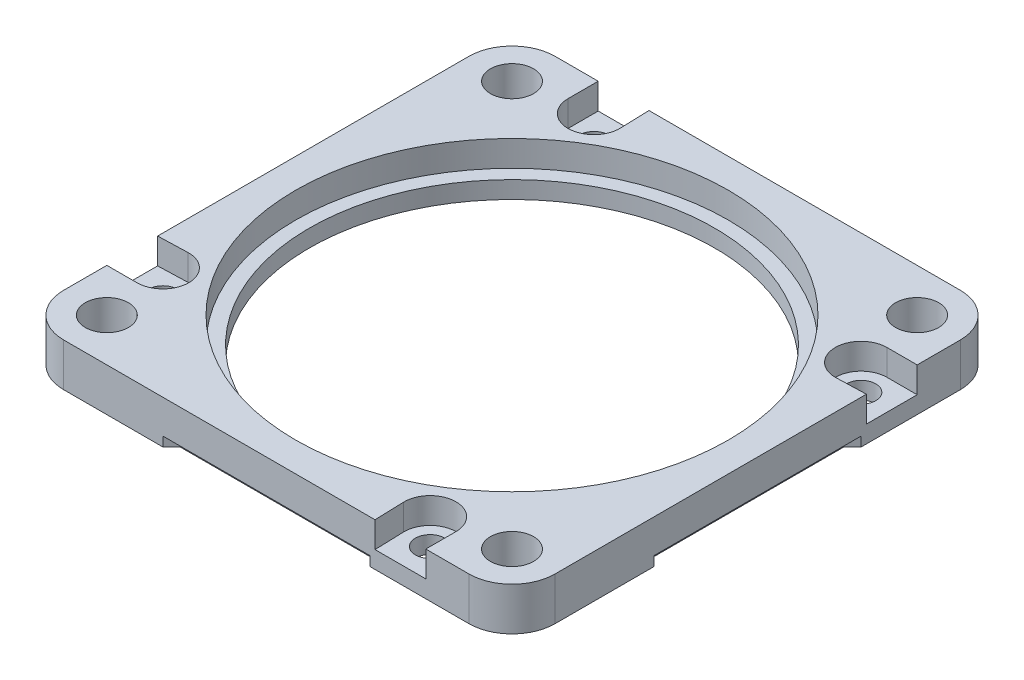
SolidWorks part; units mm, degrees
ref_plane "Front Plane" through (0, 0, 0) normal (0, 0, 1) x (1, 0, 0)
ref_plane "Top Plane" through (0, 0, 0) normal (0, 1, 0) x (1, 0, 0)
ref_plane "Right Plane" through (0, 0, 0) normal (1, 0, 0) x (0, 0, -1)
sketch "Sketch1" plane through (0, 0, 0) normal (0, 1, 0) x (1, 0, 0)
  line L1 (28.5, -28.5) -> (-28.5, -28.5)
  line L2 (28.5, -28.5) -> (28.5, 28.5)
  line L3 (28.5, 28.5) -> (-28.5, 28.5)
  line L4 (-28.5, -28.5) -> (-28.5, 28.5)
  line L5 (28.5, -28.5) -> (-28.5, 28.5) construction
  line L6 (28.5, 28.5) -> (-28.5, -28.5) construction
  circle A0 centre (0, 0) radius 25.1
  circle A1 centre (0, 0) radius 23.5
  point P0 (0, 0)
  dimension "D2" = 47
  dimension "D3" = 50.2
  dimension "D1" = 57
extrude "Boss-Extrude1" add sketch "Sketch1" along normal blind 5 contours L4 L1 L2 L3 A0 region at (0, 0, 27.6939)
extrude "Boss-Extrude2" add sketch "Sketch1<3>" along normal blind 2 contours A0 A1 region at (-24.3901, 0, 0)
sketch "Sketch1<3>" plane through (0, 0, 0) normal (0, 1, 0) x (1, 0, 0) same geometry as "Sketch1"
fillet "Fillet1" radius 5 4 edges at (-28.5, 2.5, -28.5) (28.5, 2.5, -28.5) (-28.5, 2.5, 28.5) (28.5, 2.5, 28.5)
sketch "Sketch2" plane through (0, 5, 0) normal (0, 1, 0) x (1, 0, 0)
  line L4 (23.5, 28.5) -> (-23.5, 28.5)
  line L5 (-28.5, 23.5) -> (-28.5, -23.5)
  line L6 (-23.5, -28.5) -> (23.5, -28.5)
  line L7 (28.5, -23.5) -> (28.5, 23.5)
  line L8 (23.5, 28.5) -> (-23.5, 28.5)
  line L9 (-28.5, 23.5) -> (-28.5, -23.5)
  line L10 (-23.5, -28.5) -> (23.5, -28.5)
  line L11 (28.5, -23.5) -> (28.5, 23.5)
  circle A0 centre (-23.5, 23.5) radius 2.5
  circle A1 centre (-15.5, 25) radius 1.7
  circle A2 centre (0, 0) radius 25.1 construction
  circle A3 centre (0, 0) radius 25.1
  arc A4 (-23.5, 28.5) -> (-28.5, 23.5) centre (-23.5, 23.5) ccw
  arc A5 (-28.5, -23.5) -> (-23.5, -28.5) centre (-23.5, -23.5) ccw
  arc A6 (23.5, -28.5) -> (28.5, -23.5) centre (23.5, -23.5) ccw
  arc A7 (28.5, 23.5) -> (23.5, 28.5) centre (23.5, 23.5) ccw
  arc A8 (-23.5, 28.5) -> (-28.5, 23.5) centre (-23.5, 23.5) ccw
  arc A9 (-28.5, -23.5) -> (-23.5, -28.5) centre (-23.5, -23.5) ccw
  arc A10 (23.5, -28.5) -> (28.5, -23.5) centre (23.5, -23.5) ccw
  arc A11 (28.5, 23.5) -> (23.5, 28.5) centre (23.5, 23.5) ccw
  circle A12 centre (0, 0) radius 23.5 construction
  circle A13 centre (0, 0) radius 23.5
  point P13 (0, 0)
  point P17 (-23.3059, 23.4236)
  dimension "D2" = 5
  dimension "D3" = 3.4
  dimension "D5" = 3.5
  dimension "D4" = 8
  dimension "D1" = 0
extrude "Cut-Extrude2" cut sketch "Sketch2" against normal through all contours A0 | A1 region at (-23.5, 5, -23.5) region at (-15.5, 5, -25)
sketch "Sketch3" plane through (0, 5, 0) normal (0, 1, 0) x (1, 0, 0)
  line L0 (-12.5016, 25.0966) -> (-12.6113, 28.5)
  line L1 (23.5, 28.5) -> (-23.5, 28.5) construction
  line L2 (-18.5, 25) -> (-18.5, 28.5)
  line L7 (23.5, 28.5) -> (-23.5, 28.5)
  line L8 (-28.5, 23.5) -> (-28.5, -23.5)
  line L9 (-23.5, -28.5) -> (23.5, -28.5)
  line L10 (28.5, -23.5) -> (28.5, 23.5)
  line L11 (23.5, 28.5) -> (-23.5, 28.5)
  line L12 (-28.5, 23.5) -> (-28.5, -23.5)
  line L13 (-23.5, -28.5) -> (23.5, -28.5)
  line L14 (28.5, -23.5) -> (28.5, 23.5)
  circle A0 centre (-15.5, 25) radius 1.7 construction
  circle A1 centre (-15.5, 25) radius 1.7
  arc A2 (-18.5, 25) -> (-12.5016, 25.0966) centre (-15.5, 25) ccw
  arc A7 (-23.5, 28.5) -> (-28.5, 23.5) centre (-23.5, 23.5) ccw
  arc A8 (-28.5, -23.5) -> (-23.5, -28.5) centre (-23.5, -23.5) ccw
  arc A9 (23.5, -28.5) -> (28.5, -23.5) centre (23.5, -23.5) ccw
  arc A10 (28.5, 23.5) -> (23.5, 28.5) centre (23.5, 23.5) ccw
  arc A11 (-23.5, 28.5) -> (-28.5, 23.5) centre (-23.5, 23.5) ccw
  arc A12 (-28.5, -23.5) -> (-23.5, -28.5) centre (-23.5, -23.5) ccw
  arc A13 (23.5, -28.5) -> (28.5, -23.5) centre (23.5, -23.5) ccw
  arc A14 (28.5, 23.5) -> (23.5, 28.5) centre (23.5, 23.5) ccw
  circle M11 centre (-15.5, 25) radius 1.7
  line M13 (23.5, 28.5) -> (-23.5, 28.5)
  dimension "D1" = 6
  dimension "D2" = 0
extrude "Cut-Extrude3" cut sketch "Sketch3" against normal blind 3 contours L2 A2 L0 M13 M11 region at (-15.4531, 5, -22.0888)
sketch "Sketch4" plane through (0, 0, 0) normal (0, -1, 0) x (1, 0, 0)
  line L0 (0, 0) -> (-45.5798, 0) construction
  line L1 (-27.5, -11) -> (-27.5, 11)
  line L2 (-27.5, 11) -> (-28.5, 12)
  line L3 (-28.5, 23.5) -> (-28.5, -23.5) construction
  line L4 (-27.5, -11) -> (-28.5, -12)
  line L5 (-28.5, -12) -> (-28.5, 12)
  point P1 (-28.5, 11.9741)
  point P10 (-27.5, 0)
  dimension "D1" = 11
  dimension "D2" = 1
  dimension "D3" = 135
extrude "Cut-Extrude4" cut sketch "Sketch4" against normal blind 1.1
pattern_circular "CirPattern1" count 4 over 360 about axis through (0, 2, 0) along (0, 1, 0) of "Cut-Extrude4", "Cut-Extrude3", "Cut-Extrude2"
